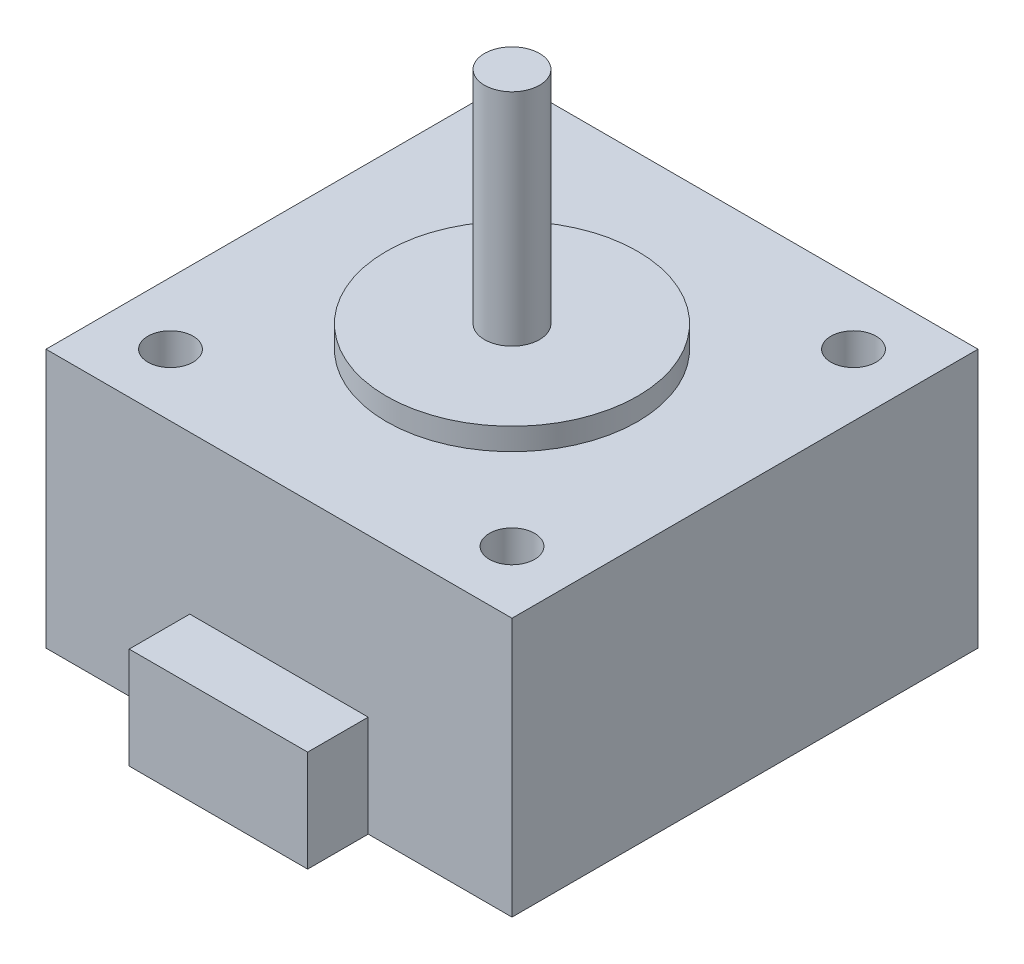
SolidWorks part; units mm, degrees
ref_plane "Спереди" through (0, 0, 0) normal (0, 0, 1) x (1, 0, 0)
ref_plane "Сверху" through (0, 0, 0) normal (0, 1, 0) x (1, 0, 0)
ref_plane "Справа" through (0, 0, 0) normal (1, 0, 0) x (0, 0, -1)
other "Configuration Table"
sketch "Sketch1" plane through (0, 0, 0) normal (0, 1, 0) x (1, 0, 0)
  line L1 (-21.15, -21.15) -> (21.15, -21.15)
  line L2 (-21.15, -21.15) -> (-21.15, 21.15)
  line L3 (-21.15, 21.15) -> (21.15, 21.15)
  line L4 (21.15, -21.15) -> (21.15, 21.15)
  line L5 (-21.15, -21.15) -> (21.15, 21.15) construction
  line L6 (-21.15, 21.15) -> (21.15, -21.15) construction
  point P0 (0, 0)
  dimension "D1" = 42.3
  dimension "D2" = 42.3
extrude "Boss-Extrude1" add sketch "Sketch1" against normal blind 23.5
sketch "Sketch2" plane through (0, 0, 0) normal (0, 1, 0) x (1, 0, 0)
  line L0 (0, 0) -> (15.5, 0) construction
  line L1 (-15.5, -15.5) -> (15.5, -15.5)
  line L2 (-15.5, -15.5) -> (-15.5, 15.5)
  line L3 (-15.5, 15.5) -> (15.5, 15.5)
  line L4 (15.5, -15.5) -> (15.5, 15.5)
  line L5 (-15.5, -15.5) -> (15.5, 15.5) construction
  line L6 (-15.5, 15.5) -> (15.5, -15.5) construction
  line L7 (0, 0) -> (0, 15.5) construction
  circle A0 centre (-15.5, 15.5) radius 2.05
  circle A1 centre (15.5, 15.5) radius 2.05
  circle A2 centre (15.5, -15.5) radius 2.05
  circle A3 centre (-15.5, -15.5) radius 2.05
  point P0 (0, 0)
  dimension "D3" = 4.1
  dimension "D1" = 31
  dimension "D2" = 31
extrude "Cut-Extrude1" cut sketch "Sketch2" against normal blind 4.5 contours A1 L4 L3 | A1 L3 L4 | A3 | A0 | A2 region at (14.63, 0, -14.63) region at (15.79, 0, -15.79)
sketch "Sketch3" plane through (0, 0, 0) normal (0, 1, 0) x (1, 0, 0)
  circle A0 centre (0, 0) radius 11.4
  circle A1 centre (0, 0) radius 2.5
  dimension "D1" = 22.8
  dimension "D2" = 5
extrude "Boss-Extrude2" add sketch "Sketch3" along normal blind 2 contours A0
extrude "Boss-Extrude3" add sketch "Sketch3<3>" along normal blind 22 contours A1 region at (0, 0, 0)
sketch "Sketch3<3>" plane through (0, 0, 0) normal (0, 1, 0) x (1, 0, 0) same geometry as "Sketch3"
sketch "Sketch4" plane through (0, 0, 21.15) normal (0, 0, 1) x (1, 0, 0)
  line L0 (0, -23.5) -> (0, -14.3) construction
  line L1 (-21.15, -23.5) -> (21.15, -23.5) construction
  line L3 (-8.1, -23.5) -> (8.1, -23.5)
  line L4 (-8.1, -23.5) -> (-8.1, -14.3)
  line L5 (-8.1, -14.3) -> (8.1, -14.3)
  line L6 (8.1, -23.5) -> (8.1, -14.3)
  line L7 (-8.1, -23.5) -> (8.1, -14.3) construction
  line L8 (-8.1, -14.3) -> (8.1, -23.5) construction
  point P5 (0, -18.9)
  dimension "D1" = 9.2
  dimension "D2" = 16.2
extrude "Boss-Extrude4" add sketch "Sketch4" along normal blind 5.5
